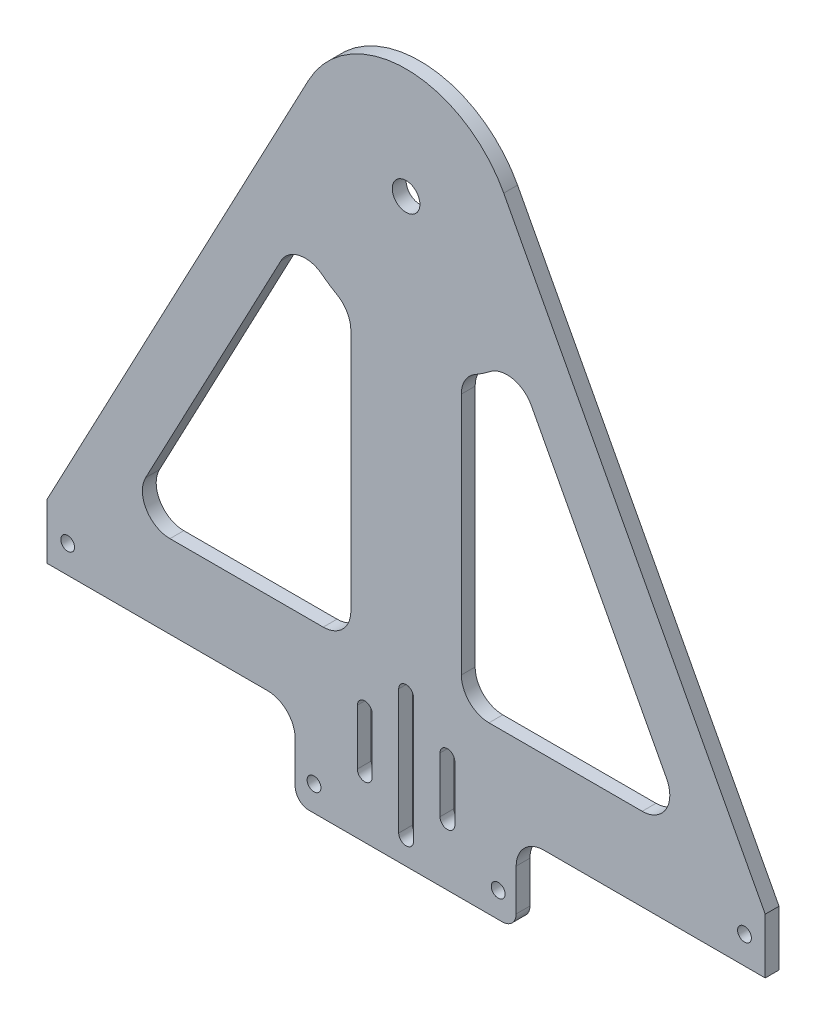
SolidWorks part; units mm, degrees
material "Hexcel AS4C (3000 Filaments)"
ref_plane "Front Plane" through (0, 0, 0) normal (0, 0, 1) x (1, 0, 0)
ref_plane "Top Plane" through (0, 0, 0) normal (0, 1, 0) x (1, 0, 0)
ref_plane "Right Plane" through (0, 0, 0) normal (1, 0, 0) x (0, 0, -1)
sketch "Sketch1" plane through (0, 0, 0) normal (0, 0, 1) x (1, 0, 0)
  line L0 (0, -58.42) -> (0, 58.42) construction
  line L2 (-82.55, 55.7897) -> (-82.55, -52.07)
  line L3 (-76.2, -58.42) -> (76.2, -58.42)
  line L4 (82.55, 55.7897) -> (82.55, -52.07)
  line L5 (-82.55, 58.42) -> (82.55, -58.42) construction
  line L6 (-82.55, -58.42) -> (82.55, 58.42) construction
  line L7 (-80.6901, 60.2799) -> (-75.4296, 65.5404)
  line L8 (-70.9395, 67.4003) -> (-50.8, 67.4003)
  line L9 (-46.3099, 65.5404) -> (-41.0494, 60.2799)
  line L10 (46.3099, 65.5404) -> (41.0494, 60.2799)
  line L11 (70.9395, 67.4003) -> (50.8, 67.4003)
  line L12 (80.6901, 60.2799) -> (75.4296, 65.5404)
  line L13 (-73.5697, 67.4003) -> (-82.55, 67.4003) construction
  line L14 (-82.55, 67.4003) -> (-82.55, 58.42) construction
  line L15 (-36.5592, 58.42) -> (0, 58.42)
  line L16 (0, 58.42) -> (36.5592, 58.42)
  circle A0 centre (-77.7875, -35.052) radius 1.5875
  circle A1 centre (-77.7875, -11.684) radius 1.5875
  circle A2 centre (-77.7875, 11.684) radius 1.5875
  circle A3 centre (-77.7875, 35.052) radius 1.5875
  circle A4 centre (77.7875, 35.052) radius 1.5875
  circle A5 centre (77.7875, 11.684) radius 1.5875
  circle A6 centre (77.7875, -11.684) radius 1.5875
  circle A7 centre (77.7875, -35.052) radius 1.5875
  arc A8 (82.55, 55.7897) -> (80.6901, 60.2799) centre (76.2, 55.7897) ccw
  arc A9 (75.4296, 65.5404) -> (70.9395, 67.4003) centre (70.9395, 61.0503) ccw
  arc A10 (46.3099, 65.5404) -> (50.8, 67.4003) centre (50.8, 61.0503) cw
  arc A11 (41.0494, 60.2799) -> (36.5592, 58.42) centre (36.5592, 64.77) cw
  arc A12 (-36.5592, 58.42) -> (-41.0494, 60.2799) centre (-36.5592, 64.77) cw
  arc A13 (-46.3099, 65.5404) -> (-50.8, 67.4003) centre (-50.8, 61.0503) ccw
  arc A14 (-70.9395, 67.4003) -> (-75.4296, 65.5404) centre (-70.9395, 61.0503) ccw
  arc A15 (-82.55, 55.7897) -> (-80.6901, 60.2799) centre (-76.2, 55.7897) cw
  arc A16 (76.2, -58.42) -> (82.55, -52.07) centre (76.2, -52.07) ccw
  arc A17 (-76.2, -58.42) -> (-82.55, -52.07) centre (-76.2, -52.07) cw
  circle A18 centre (-70.9395, 61.0503) radius 1.5875
  circle A19 centre (-50.8, 61.0503) radius 1.5875
  circle A20 centre (50.8, 61.0503) radius 1.5875
  circle A21 centre (70.9395, 61.0503) radius 1.5875
  point P0 (0, 0)
  point P36 (73.5697, 67.4003)
  point P39 (48.1697, 67.4003)
  point P42 (39.1895, 58.42)
  point P45 (-39.1895, 58.42)
  point P48 (-48.1697, 67.4003)
  dimension "D3" = 3.175
  dimension "D11" = 6.35
  dimension "D12" = 6.35
  dimension "D13" = 3.175
  dimension "D14" = 3.175
  dimension "D1" = 165.1
  dimension "D2" = 116.84
  dimension "D4" = 23.368
  dimension "D5" = 4.7625
  dimension "D7" = 46.736
  dimension "D8" = 12.7
  dimension "D9" = 135
  dimension "D10" = 25.4
  dimension "D6" = 4
extrude "Boss-Extrude1" [suppressed] add sketch "Sketch1" along normal blind 1.5
sketch "Sketch2" [suppressed] plane through (0, 0, 1.5) normal (0, 0, 1) x (1, 0, 0)
  line L0 (0, -45.72) -> (0, 6.3634) construction
  line L1 (0, -58.42) -> (0, 63.5) construction
  line L3 (-82.55, 1.8599) -> (82.55, 1.8599) construction
  line L4 (-82.55, 55.7897) -> (-82.55, -52.07) construction
  line L5 (82.55, -52.07) -> (82.55, 55.7897) construction
  line L7 (-76.2, -58.42) -> (76.2, -58.42) construction
  circle A0 centre (0, -45.72) radius 1.9062
  circle A1 centre (0, 6.3634) radius 1.9062
  dimension "D2" = 3.8125
  dimension "D3" = 3.8125
  dimension "D1" = 52.0834
  dimension "D4" = 12.7
extrude "Cut-Extrude1" [suppressed] cut sketch "Sketch2" against normal through all
sketch "Sketch3" [suppressed] plane through (0, 0, 1.5) normal (0, 0, 1) x (1, 0, 0)
  line L0 (0, 50.8) -> (0, 30.8) construction
  line L1 (-10, 40.8) -> (10, 40.8) construction
  line L2 (-10, 40.8) -> (0, 50.8) construction
  line L3 (0, 50.8) -> (10, 40.8) construction
  line L4 (10, 40.8) -> (0, 30.8) construction
  line L5 (0, 30.8) -> (-10, 40.8) construction
  line L6 (0, 63.5) -> (0, -58.42) construction
  line L8 (-76.2, -58.42) -> (76.2, -58.42) construction
  circle A0 centre (0, 50.8) radius 1.8669
  circle A1 centre (-10, 40.8) radius 1.8669
  circle A2 centre (0, 30.8) radius 1.8669
  circle A3 centre (10, 40.8) radius 1.8669
  dimension "D1" = 3.7338
  dimension "D2" = 12.7
extrude "Cut-Extrude2" [suppressed] cut sketch "Sketch3" against normal through all
sketch "Sketch4" [suppressed] plane through (0, 0, 1.5) normal (0, 0, 1) x (1, 0, 0)
  line L0 (0, 58.42) -> (0, -58.42) construction
  line L1 (36.5592, 58.42) -> (-36.5592, 58.42) construction
  line L2 (-76.2, -58.42) -> (76.2, -58.42) construction
  line L5 (0, 33.045) -> (0, 52.045) construction
  line L6 (-9.5, 42.545) -> (9.5, 42.545) construction
  circle A14 centre (0, 42.545) radius 8 construction
  circle A15 centre (0, 42.545) radius 9.5 construction
  circle A16 centre (0, 50.545) radius 1.5
  circle A17 centre (0, 34.545) radius 1.5
  circle A18 centre (-9.5, 42.545) radius 1.5
  circle A19 centre (9.5, 42.545) radius 1.5
  dimension "D1" = 15.875
  dimension "D3" = 16
  dimension "D4" = 19
  dimension "D5" = 3
  dimension "D6" = 3
  dimension "D7" = 3
  dimension "D8" = 3
extrude "Cut-Extrude3" [suppressed] cut sketch "Sketch4" against normal through all
sketch "Sketch5" plane through (0, 0, 0) normal (0, 0, 1) x (1, 0, 0)
  line L0 (0, 70.8856) -> (0, 39.1356) construction
  line L1 (-82.55, 70.8856) -> (82.55, 70.8856) construction
  line L2 (-82.55, 70.8856) -> (-82.55, 58.1856)
  line L4 (82.55, 70.8856) -> (82.55, 58.1856)
  line L5 (82.55, 70.8856) -> (22.4464, 184.3733)
  line L8 (77.7875, 58.1856) -> (77.7875, 70.8856) construction
  line L11 (0, -48.26) -> (0, -46.3538) construction
  line L12 (0, 70.8856) -> (0, 172.4856) construction
  line L14 (-82.55, 58.1856) -> (-31.849, 58.1856)
  line L15 (-22.324, 39.1356) -> (22.126, 39.1356)
  line L16 (-25.499, 42.3106) -> (-25.499, 51.8356)
  line L17 (25.301, 42.3106) -> (25.301, 51.8356)
  line L18 (31.651, 58.1856) -> (82.55, 58.1856)
  line L19 (-82.55, 70.8856) -> (-22.4464, 184.3733)
  line L20 (-77.7875, 58.1856) -> (-77.7875, 70.8856) construction
  line L23 (0, -0.6801) -> (0, 0) construction
  line L24 (0, 39.1356) -> (0, 70.8856) construction
  line L26 (0, 70.8856) -> (-82.55, 70.8856) construction
  line L27 (-59.879, 86.5575) -> (-28.8054, 145.2308)
  line L28 (0, -48.26) -> (0, -46.3538) construction
  line L37 (68.1789, 70.8856) -> (11.2232, 178.4295) construction
  line L38 (31.651, 70.8856) -> (68.1789, 70.8856) construction
  line L39 (12.601, 51.8356) -> (12.601, 51.8356) construction
  line L40 (-12.799, 51.8356) -> (12.601, 51.8356) construction
  line L41 (-12.799, 51.8356) -> (-12.799, 51.8356) construction
  line L42 (-68.1789, 70.8856) -> (-31.849, 70.8856) construction
  line L43 (-12.7, 83.5856) -> (-12.7, 139.49)
  line L44 (-68.1789, 70.8856) -> (-11.2232, 178.4295) construction
  line L45 (68.1789, 70.8856) -> (68.1789, 70.8856) construction
  line L46 (-54.2674, 77.2356) -> (-19.05, 77.2356)
  line L47 (-12.7, 70.8856) -> (-12.7, 172.4856) construction
  line L48 (19.05, 77.2356) -> (54.2674, 77.2356) construction
  line L49 (-82.55, 77.2356) -> (82.55, 77.2356) construction
  line L50 (-68.1789, 70.8856) -> (-68.1789, 70.8856) construction
  line L51 (59.879, 86.5575) -> (28.8054, 145.2308)
  line L52 (54.2674, 77.2356) -> (19.05, 77.2356)
  line L53 (12.7, 83.5856) -> (12.7, 139.49)
  line L54 (-11.2, 52.9151) -> (-11.2, 65.6151)
  line L55 (-7.8, 52.9151) -> (-7.8, 65.6151)
  line L56 (-1.7, 44.9151) -> (-1.7, 73.6151)
  line L57 (1.7, 44.9151) -> (1.7, 73.6151)
  line L58 (7.8, 52.9151) -> (7.8, 65.6151)
  line L59 (11.2, 52.9151) -> (11.2, 65.6151)
  arc A12 (-25.499, 51.8356) -> (-31.849, 58.1856) centre (-31.849, 51.8356) ccw
  arc A13 (25.301, 51.8356) -> (31.651, 58.1856) centre (31.651, 51.8356) cw
  arc A14 (25.301, 42.3106) -> (22.126, 39.1356) centre (22.126, 42.3106) cw
  arc A15 (-25.499, 42.3106) -> (-22.324, 39.1356) centre (-22.324, 42.3106) ccw
  circle A16 centre (-77.7875, 64.5356) radius 1.5875
  circle A17 centre (77.7875, 64.5356) radius 1.5875
  arc A18 (22.4464, 184.3733) -> (-22.4464, 184.3733) centre (0, 172.4856) ccw
  circle A19 centre (0, 172.4856) radius 25.4 construction
  arc A25 (11.2232, 178.4295) -> (-11.2232, 178.4295) centre (0, 172.4856) ccw construction
  arc A26 (12.601, 51.8356) -> (31.651, 70.8856) centre (31.651, 51.8356) cw construction
  arc A27 (-12.799, 51.8356) -> (-31.849, 70.8856) centre (-31.849, 51.8356) ccw construction
  arc A28 (12.601, 51.8356) -> (12.601, 51.8356) centre (12.601, 51.8356) cw construction
  arc A29 (-12.799, 51.8356) -> (-12.799, 51.8356) centre (-12.799, 51.8356) ccw construction
  arc A30 (-19.3282, 147.2966) -> (-15.875, 144.9893) centre (0, 172.4856) ccw
  arc A31 (-19.3282, 147.2966) -> (-28.8054, 145.2308) centre (-23.1938, 142.2588) ccw
  circle A32 centre (0, 172.4856) radius 31.75 construction
  arc A33 (-15.875, 144.9893) -> (-12.7, 139.49) centre (-19.05, 139.49) cw
  arc A34 (-19.05, 77.2356) -> (-12.7, 83.5856) centre (-19.05, 83.5856) ccw
  arc A35 (-54.2674, 77.2356) -> (-59.879, 86.5575) centre (-54.2674, 83.5856) cw
  arc A36 (15.875, 144.9893) -> (12.7, 139.49) centre (19.05, 139.49) ccw
  arc A37 (19.3282, 147.2966) -> (15.875, 144.9893) centre (0, 172.4856) cw
  arc A38 (19.3282, 147.2966) -> (28.8054, 145.2308) centre (23.1938, 142.2588) cw
  arc A39 (54.2674, 77.2356) -> (59.879, 86.5575) centre (54.2674, 83.5856) ccw
  arc A40 (19.05, 77.2356) -> (12.7, 83.5856) centre (19.05, 83.5856) cw
  circle A57 centre (0, 52.9151) radius 8 construction
  circle A58 centre (0, 52.9151) radius 9.5 construction
  arc A59 (7.8, 52.9151) -> (11.2, 52.9151) centre (9.5, 52.9151) ccw
  arc A60 (-11.2, 52.9151) -> (-7.8, 52.9151) centre (-9.5, 52.9151) ccw
  arc A62 (-1.7, 44.9151) -> (1.7, 44.9151) centre (0, 44.9151) ccw
  arc A63 (-7.8, 65.6151) -> (-11.2, 65.6151) centre (-9.5, 65.6151) ccw
  arc A64 (11.2, 65.6151) -> (7.8, 65.6151) centre (9.5, 65.6151) ccw
  arc A65 (1.7, 73.6151) -> (-1.7, 73.6151) centre (0, 73.6151) ccw
  circle A66 centre (-21.1667, 44.969) radius 1.5875
  circle A67 centre (21.1667, 44.969) radius 1.5875
  circle A68 centre (0, 172.4856) radius 3.175
  point P0 (0, 0)
  point P52 (25.301, 58.1856)
  point P55 (25.301, 39.1356)
  point P58 (-25.499, 39.1356)
  point P68 (30.3627, 182.0028)
  dimension "D17" = 6.35
  dimension "D18" = 6.35
  dimension "D19" = 3.175
  dimension "D20" = 3.175
  dimension "D21" = 3.175
  dimension "D4" = 50.8
  dimension "D24" = 6.35
  dimension "D25" = 16
  dimension "D26" = 19
  dimension "D27" = 3.4
  dimension "D28" = 3.4
  dimension "D30" = 3.4
  dimension "D31" = 3.4
  dimension "D32" = 3.4
  dimension "D35" = 3.4
  dimension "D36" = 3.175
  dimension "D9" = 6.35
  dimension "D14" = 12.7
  dimension "D15" = 50.8
  dimension "D16" = 19.05
  dimension "D22" = 6.35
  dimension "D3" = 101.6
  dimension "D33" = 12.7
  dimension "D34" = 12.7
  dimension "D8" = 25.9166
  dimension "D10" = 165.1
  dimension "D6" = 6.35
  dimension "D7" = 12.7
  dimension "D23" = 6.35
extrude "Boss-Extrude2" add sketch "Sketch5" along normal blind 3.175
equation "\"Top Plate Width\" = 4.5in"
equation "\"Plate Width\" = 3.5in"
equation "\"Plate Thickness\" = 0.375in"
equation "\"Num holes\" = 4"
equation "\"Plate Height\" = 1.25in"
equation "\"Plate Clearance Hole Diameter\" = 0.125in"
equation "\"D3@Sketch1\"=\"Plate Clearance Hole Diameter\""
equation "\"Hole Spacing\"= \"Plate Width\" / ( \"Num holes\" + 1 )"
equation "\"Plate Tap Hole Diameter\" = 0.116in"
equation "\"Bottom Plate Length\" = 6.5in"
equation "\"D21@Sketch5\"=\"Plate Clearance Hole Diameter\""
equation "\"Number Eight Clearance Size\" = 0.177in"
equation "\"Back Brace Height\" = 1.1962912in"
equation "\"Titanium Offset Length\" = 4in"
equation "\"Titanium Head Radius\" = 2in"
equation "\"D3@Sketch5\"=\"Titanium Offset Length\""
equation "\"D4@Sketch5\"=\"Titanium Head Radius\""
equation "\"Titanium Plate Border Thickness\" = 0.5in"
equation "\"D5@Sketch5\"=\"Titanium Plate Border Thickness\""
equation "\"D6@Sketch5\"=\"Titanium Plate Border Thickness\" / 2"
equation "\"D23@Sketch5\"=\"Titanium Plate Border Thickness\"/2"
equation "\"slot_hole_length\"=0.75"
